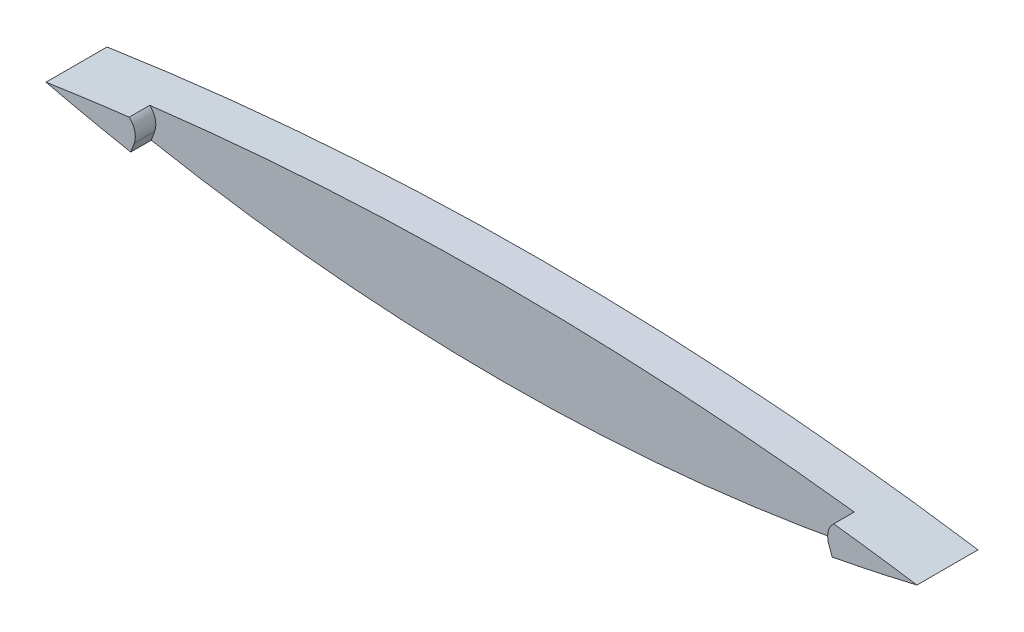
SolidWorks part; units mm, degrees
material "ABS PC"
ref_plane "Front Plane" through (0, 0, 0) normal (0, 0, 1) x (1, 0, 0)
ref_plane "Top Plane" through (0, 0, 0) normal (0, 1, 0) x (1, 0, 0)
ref_plane "Right Plane" through (0, 0, 0) normal (1, 0, 0) x (0, 0, -1)
sketch "Sketch1" plane through (0, 0, 0) normal (0, 0, 1) x (1, 0, 0)
  line L0 (-23.3537, 0) -> (23.3537, 0) construction
  arc A0 (-23.3537, 0) -> (23.3537, 0) centre (0, 97.9392) ccw
  arc A1 (23.3537, 0) -> (-23.3537, 0) centre (0, -154.5216) ccw
  dimension "D1" = 100.685
  dimension "D2" = 156.2764
  dimension "D3" = 46.7073
extrude "Extrude1" add sketch "Sketch1" along normal mid plane 2.1721
sketch "Sketch5" plane through (0, 0, 1.086) normal (0, 0, 1) x (1, 0, 0)
  line L1 (-18.8083, -0.9735) -> (-18.625, -0.4701)
  line L2 (-18.8083, -0.9735) -> (-20.4607, -0.6593) construction
  line L3 (18.8083, -0.9735) -> (20.4607, -0.6593) construction
  line L4 (0, 3.966) -> (0, -7.081) construction
  line L5 (18.8083, -0.9735) -> (18.625, -0.4701)
  arc A1 (-18.625, -0.4701) -> (-18.8889, 0.6091) centre (-19.5647, -0.128) ccw
  arc A4 (18.8889, 0.6091) -> (23.3537, 0) centre (0, -154.5216) cw
  arc A5 (23.3537, 0) -> (-23.3537, 0) centre (0, -154.5216) ccw construction
  arc A6 (-23.3537, 0) -> (23.3537, 0) centre (0, 97.9392) ccw construction
  arc A7 (23.3537, 0) -> (18.8083, -0.9735) centre (0, 97.9392) cw
  arc A8 (-23.3537, 0) -> (-18.8083, -0.9735) centre (0, 97.9392) ccw
  arc A9 (-18.8889, 0.6091) -> (-23.3537, 0) centre (0, -154.5216) ccw
  arc A10 (18.625, -0.4701) -> (18.8889, 0.6091) centre (19.5647, -0.128) cw
  dimension "D5" = 1
  dimension "D3" = 99.234
  dimension "D1" = 4.5061
  dimension "D2" = 4.6485
  dimension "D4" = 0.5358
extrude "Extrude2" add sketch "Sketch5" along normal blind 1.1
